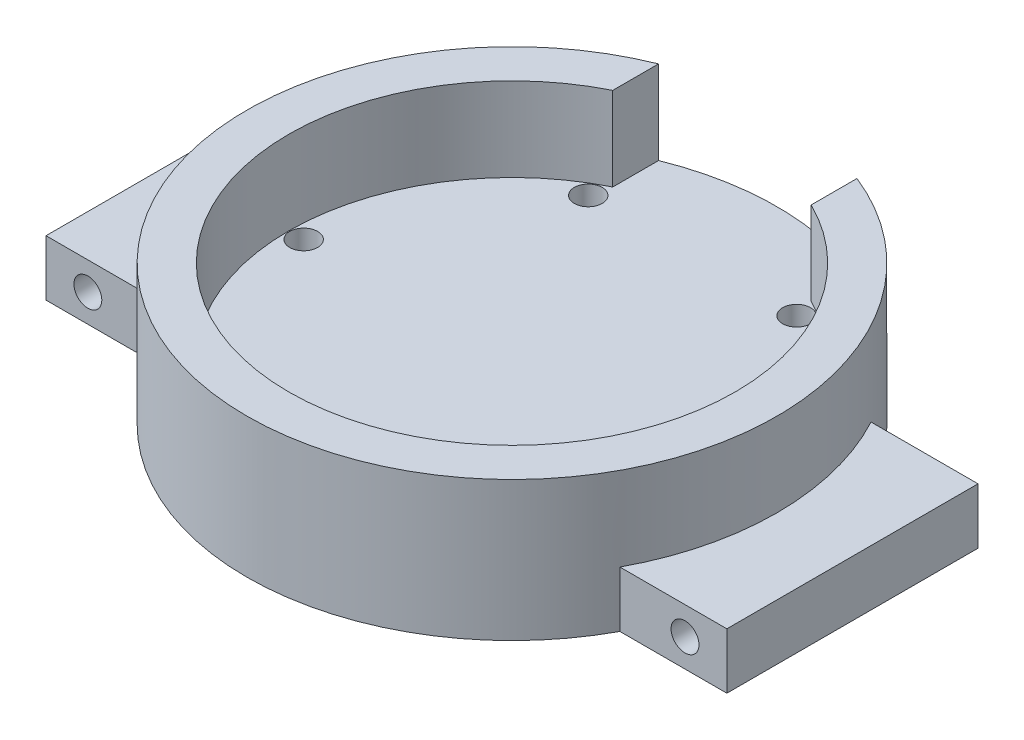
SolidWorks part; units mm, degrees
ref_plane "Front Plane" through (0, 0, 0) normal (0, 0, 1) x (1, 0, 0)
ref_plane "Top Plane" through (0, 0, 0) normal (0, 1, 0) x (1, 0, 0)
ref_plane "Right Plane" through (0, 0, 0) normal (1, 0, 0) x (0, 0, -1)
sketch "Sketch7" plane through (0, 0, 0) normal (0, 1, 0) x (1, 0, 0)
  line L1 (-61, 0) -> (61, 0)
  line L2 (-61, 0) -> (-61, 45)
  line L3 (-61, 45) -> (61, 45)
  line L4 (61, 0) -> (61, 45)
  dimension "D1" = 45
  dimension "D2" = 122
extrude "Boss-Extrude1" add sketch "Sketch7" along normal blind 10
sketch "Sketch9" plane through (0, 10, 0) normal (0, 1, 0) x (1, 0, 0)
  line L0 (-61, 45) -> (-61, 0) construction
  circle A0 centre (0, 22.5) radius 37.333 construction
  circle A1 centre (0, 22.5) radius 42.333
  circle A2 centre (-37.333, 22.5) radius 2.5
  circle A3 centre (-18.6665, 54.8313) radius 2.5
  circle A4 centre (18.6665, 54.8313) radius 2.5
  circle A5 centre (37.333, 22.5) radius 2.5
  circle A6 centre (18.6665, -9.8313) radius 2.5
  circle A7 centre (-18.6665, -9.8313) radius 2.5
  point P6 (-61, 22.5)
  dimension "D1" = 74.666
  dimension "D2" = 5
  dimension "D3" = 5
  dimension "D4" = 6
extrude "Boss-Extrude2" add sketch "Sketch9" against normal up to surface (10 mm away) up to face at (0, 0, -22.5)
extrude "Cut-Extrude4" cut sketch "Sketch9<2>" against normal through all contours A2 | A5
sketch "Sketch9<2>" plane through (0, 10, 0) normal (0, 1, 0) x (1, 0, 0) same geometry as "Sketch9"
sketch "Sketch10" plane through (0, 0, 0) normal (0, -1, 0) x (1, 0, 0)
  circle A0 centre (0, -22.5) radius 40
  arc A1 (35.8585, 0) -> (-35.8585, 0) centre (0, -22.5) ccw construction
  circle A2 centre (0, -22.5) radius 47.5
  line M5 (-61, -45) -> (-35.8585, -45)
  arc M6 (-35.8585, -45) -> (35.8585, -45) centre (0, -22.5) ccw
  line M7 (35.8585, -45) -> (61, -45)
  line M9 (61, 0) -> (35.8585, 0)
  arc M10 (35.8585, 0) -> (-35.8585, 0) centre (0, -22.5) ccw
  line M11 (-35.8585, 0) -> (-61, 0)
  dimension "D1" = 80
  dimension "D2" = 7.5
extrude "Boss-Extrude3" add sketch "Sketch10" against normal blind 25 contours A2 M5 M7 M6 | A2 A0 M7 M9 M10 M11 M5 M6 | A2 M9 M11 M10 | A2 | A0 region at (44.8275, 0, -33.7905) region at (38.8458, 0, 0.8732) region at (0, 0, -69.1268)
sketch "Sketch11" plane through (0, 0, 0) normal (0, 0, 1) x (1, 0, 0)
  line L0 (61, 10) -> (61, 0) construction
  line L1 (-61, 10) -> (-61, 0) construction
  circle A0 centre (-53.5, 5) radius 2.5
  circle A1 centre (53.5, 5) radius 2.5
  point P8 (-61, 5)
  dimension "D2" = 5
  dimension "D1" = 7.5
  dimension "D3" = 7.5
extrude "Cut-Extrude5" cut sketch "Sketch11" against normal through all
sketch "Sketch12" plane through (0, 10, 0) normal (0, 1, 0) x (1, 0, 0)
  line L0 (-17.78, 58.3312) -> (-17.78, 66.5468)
  line L1 (17.78, 58.3312) -> (17.78, 66.5468)
  arc A0 (17.78, 58.3312) -> (-17.78, 58.3312) centre (0, 22.5) ccw
  circle A1 centre (0, 22.5) radius 40 construction
  arc A2 (17.78, 66.5468) -> (-17.78, 66.5468) centre (0, 22.5) ccw
  circle A3 centre (0, 22.5) radius 47.5 construction
  circle A4 centre (0, 22.5) radius 40 construction
  point P1 (0, 62.5)
  point P10 (-7.5841, 61.7744)
  dimension "D1" = 35.56
extrude "Cut-Extrude6" cut sketch "Sketch12" along normal through all
